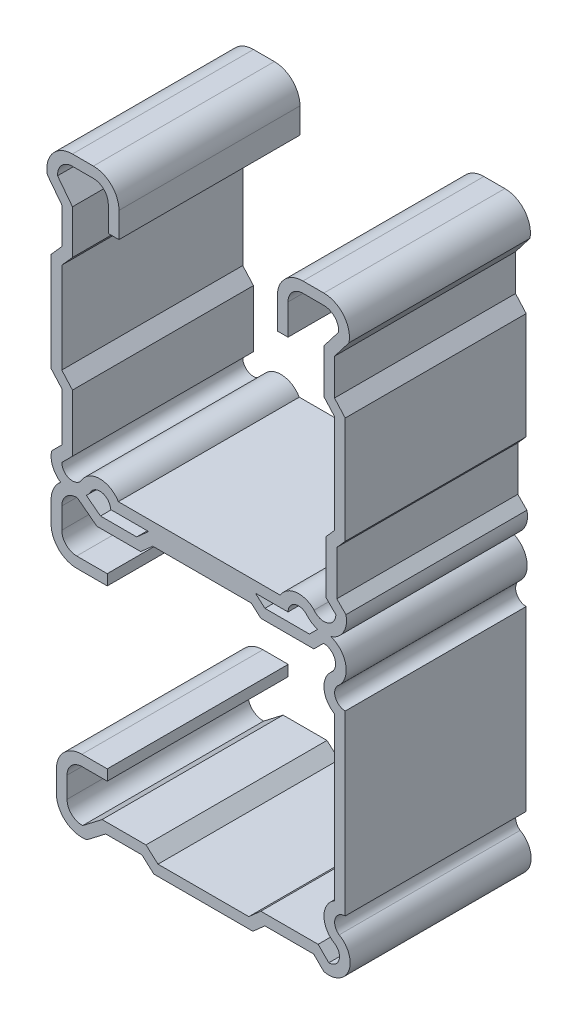
SolidWorks part; units mm, degrees
note: '?' marks a value the reader was unsure of.
ref_plane "Plane1" through (0, 0, 0) normal (0, 0, 1) x (1, 0, 0)
ref_plane "Plane2" through (0, 0, 0) normal (0, 1, 0) x (1, 0, 0)
ref_plane "Plane3" through (0, 0, 0) normal (1, 0, 0) x (0, 0, -1)
sketch "Sketch1" plane through (-20.32, 17.78, 0) normal (0, 0, 1) x (1, 0, 0)
  line L0 (17.3228, 17.0759) -> (19.4124, 19.8001)
  line L1 (17.6403, -13.3787) -> (19.0032, -14.7415)
  line L2 (-17.9578, -13.9795) -> (-19.4564, -15.4781)
  line L4 (-17.9578, -13.9795) -> (-17.9578, -5.9368)
  line L5 (17.3228, 21.9964) -> (14.3858, 21.9964)
  line L6 (12.2936, 19.9042) -> (12.2936, 15.6146)
  line L7 (-17.9578, -5.9368) -> (-19.4564, -4.2539)
  line L8 (-12.9286, 19.1676) -> (-12.9286, 15.6146)
  line L10 (-19.4564, -4.2539) -> (-19.4564, 8.4957)
  line L11 (-17.9578, 10.1786) -> (-19.4564, 8.4957)
  line L12 (-17.9578, 10.1786) -> (-17.9578, 16.3393)
  line L13 (-17.9578, 16.3393) -> (-20.0474, 19.0635)
  line L14 (-17.9578, 21.2598) -> (-15.0208, 21.2598)
  line L16 (17.6403, -13.3787) -> (17.6403, -5.9368)
  line L17 (17.3228, 10.9152) -> (17.3228, 17.0759)
  line L18 (-11.43, 19.1676) -> (-11.43, 15.6146)
  line L19 (-17.9578, 22.7584) -> (-15.0208, 22.7584)
  line L20 (-19.4564, 15.8307) -> (-21.4799, 18.4689)
  line L21 (-19.4564, 10.7491) -> (-19.4564, 15.8307)
  line L22 (-19.4564, 10.7491) -> (-20.955, 9.0662)
  line L23 (-20.955, -4.8244) -> (-20.955, 9.0662)
  line L24 (-19.4564, -6.5073) -> (-20.955, -4.8244)
  line L25 (18.8214, -4.6104) -> (18.8214, 9.2323)
  line L26 (-19.4564, -13.3588) -> (-19.4564, -6.5073)
  line L27 (-19.4564, -13.3588) -> (-20.871, -14.7733)
  line L28 (10.795, 19.9042) -> (10.795, 15.6146)
  line L29 (17.3228, 23.495) -> (14.3858, 23.495)
  line L30 (18.8214, 16.5673) -> (20.8449, 19.2055)
  line L31 (18.8214, 11.4857) -> (18.8214, 16.5673)
  line L32 (18.8214, 11.4857) -> (20.32, 9.8028)
  line L33 (20.32, -5.181) -> (20.32, 9.8028)
  line L34 (19.1389, -6.5073) -> (20.32, -5.181)
  line L35 (19.1389, -12.7579) -> (19.1389, -6.5073)
  line L36 (19.1389, -12.7579) -> (20.4241, -14.0431)
  line L37 (17.6403, -5.9368) -> (18.8214, -4.6104)
  line L38 (-12.6128, -17.78) -> (12.2953, -17.78)
  line L39 (17.3228, 10.9152) -> (18.8214, 9.2323)
  line L41 (-11.5242, -16.2814) -> (11.2067, -16.2814)
  line L42 (-12.9286, 15.6146) -> (-11.43, 15.6146)
  line L43 (10.795, 15.6146) -> (12.2936, 15.6146)
  arc A0 (19.0032, -14.7415) -> (15.9562, -15.7193) centre (17.3228, -14.7415) cw
  arc A1 (15.9562, -15.7193) -> (11.2067, -16.2814) centre (13.7938, -17.7947) ccw
  arc A2 (-16.7318, -16.3399) -> (-11.5242, -16.2814) centre (-14.1113, -17.7947) cw
  arc A3 (-19.4564, -15.4781) -> (-16.7318, -16.3399) centre (-17.9578, -15.4781) ccw
  arc A4 (-17.9578, 21.2598) -> (-20.0474, 19.0635) centre (-17.9578, 19.1676) ccw
  arc A5 (-12.9286, 19.1676) -> (-15.0208, 21.2598) centre (-15.0208, 19.1676) ccw
  arc A6 (17.3228, 21.9964) -> (19.4124, 19.8001) centre (17.3228, 19.9042) cw
  arc A7 (12.2936, 19.9042) -> (14.3858, 21.9964) centre (14.3858, 19.9042) cw
  arc A8 (-11.43, 19.1676) -> (-15.0208, 22.7584) centre (-15.0208, 19.1676) ccw
  arc A9 (-17.9578, 22.7584) -> (-21.4799, 18.4689) centre (-17.9578, 19.1676) ccw
  arc A10 (-20.871, -14.7733) -> (-15.3373, -16.9329) centre (-17.9578, -15.4781) ccw
  arc A11 (10.795, 19.9042) -> (14.3858, 23.495) centre (14.3858, 19.9042) cw
  arc A12 (17.3228, 23.495) -> (20.8449, 19.2055) centre (17.3228, 19.9042) cw
  arc A13 (20.4241, -14.0431) -> (15.0198, -16.9329) centre (17.3228, -14.7415) cw
  arc A14 (15.0198, -16.9329) -> (12.2953, -17.78) centre (13.7938, -17.7947) ccw
  arc A15 (-15.3373, -16.9329) -> (-12.6128, -17.78) centre (-14.1113, -17.7947) cw
  dimension "D1" = 41.275
  dimension "D9" = 7.1437
  dimension "D2" = 34.6458
  dimension "D4" = 22.225
  dimension "D3" = 36.9623
  dimension "D5" = 9.525
  dimension "D12" = 41.275
  dimension "D14" = 13.6922
extrude "Base-Extrude" add sketch "Sketch1" along normal mid plane 25.4
ref_axis "Axis1" through (0, 0, -50) along (0, 0, 1)?
pattern_circular "CirPattern1" count 2 every 90 about axis through (0, 0, 0) along (0, 0, 1) of "Base-Extrude"
